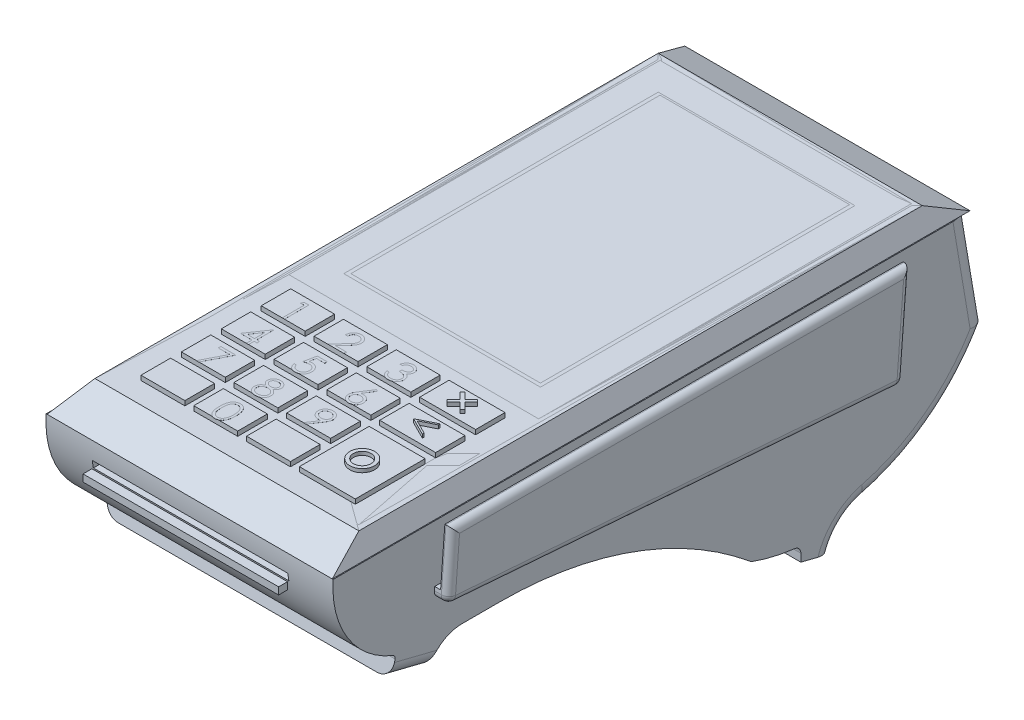
SolidWorks part; units mm, degrees
note: The reader was unsure of these and kept them because the rebuilt part matched: shared geometry of "Sketch5<2>", "Sketch7<2>", "Sketch8<2>", "Sketch9<2>".
material "ABS"
ref_plane "Front Plane" through (0, 0, 0) normal (0, 0, 1) x (1, 0, 0)
ref_plane "Top Plane" through (0, 0, 0) normal (0, 1, 0) x (1, 0, 0)
ref_plane "Right Plane" through (0, 0, 0) normal (1, 0, 0) x (0, 0, -1)
sketch "Sketch1" plane through (0, 0, 0) normal (0, 1, 0) x (1, 0, 0)
  line L1 (-35.75, -78) -> (35.75, -78)
  line L2 (-35.75, -78) -> (-35.75, 78)
  line L3 (-35.75, 78) -> (35.75, 78)
  line L4 (35.75, -78) -> (35.75, 78)
  line L5 (-35.75, -78) -> (35.75, 78) construction
  line L6 (-35.75, 78) -> (35.75, -78) construction
  point P0 (0, 0)
  dimension "D1" = 156
  dimension "D2" = 71.5
extrude "Boss-Extrude1" add sketch "Sketch1" against normal blind 5
sketch "Sketch2" plane through (0, 0, 0) normal (0, 1, 0) x (1, 0, 0)
  line L0 (-17.85, -35.4) -> (-15.35, -35.4) construction
  line L1 (-30.25, -39.55) -> (-17.85, -39.55)
  line L2 (-30.25, -39.55) -> (-30.25, -31.25)
  line L3 (-30.25, -31.25) -> (-17.85, -31.25)
  line L4 (-17.85, -39.55) -> (-17.85, -31.25)
  line L5 (-30.25, -39.55) -> (-17.85, -31.25) construction
  line L6 (-30.25, -31.25) -> (-17.85, -39.55) construction
  line L7 (-30.25, -50.825) -> (-17.85, -50.825)
  line L8 (-30.25, -50.825) -> (-30.25, -42.525)
  line L9 (-30.25, -42.525) -> (-17.85, -42.525)
  line L10 (-17.85, -50.825) -> (-17.85, -42.525)
  line L11 (-30.25, -50.825) -> (-17.85, -42.525) construction
  line L12 (-30.25, -42.525) -> (-17.85, -50.825) construction
  line L13 (-0.45, -39.55) -> (11.95, -39.55)
  line L14 (-0.45, -39.55) -> (-0.45, -31.25)
  line L15 (-0.45, -31.25) -> (11.95, -31.25)
  line L16 (11.95, -39.55) -> (11.95, -31.25)
  line L17 (-0.45, -39.55) -> (11.95, -31.25) construction
  line L18 (-0.45, -31.25) -> (11.95, -39.55) construction
  line L19 (-15.35, -39.55) -> (-2.95, -39.55)
  line L20 (-15.35, -39.55) -> (-15.35, -31.25)
  line L21 (-15.35, -31.25) -> (-2.95, -31.25)
  line L22 (-2.95, -39.55) -> (-2.95, -31.25)
  line L23 (-15.35, -39.55) -> (-2.95, -31.25) construction
  line L24 (-15.35, -31.25) -> (-2.95, -39.55) construction
  line L25 (-15.35, -50.825) -> (-2.95, -50.825)
  line L26 (-15.35, -50.825) -> (-15.35, -42.525)
  line L27 (-15.35, -42.525) -> (-2.95, -42.525)
  line L28 (-2.95, -50.825) -> (-2.95, -42.525)
  line L29 (-15.35, -50.825) -> (-2.95, -42.525) construction
  line L30 (-15.35, -42.525) -> (-2.95, -50.825) construction
  line L31 (-30.25, -62.1) -> (-17.85, -62.1)
  line L32 (-30.25, -62.1) -> (-30.25, -53.8)
  line L33 (-30.25, -53.8) -> (-17.85, -53.8)
  line L34 (-17.85, -62.1) -> (-17.85, -53.8)
  line L35 (-30.25, -62.1) -> (-17.85, -53.8) construction
  line L36 (-30.25, -53.8) -> (-17.85, -62.1) construction
  line L37 (-0.45, -50.825) -> (11.95, -50.825)
  line L38 (-0.45, -50.825) -> (-0.45, -42.525)
  line L39 (-0.45, -42.525) -> (11.95, -42.525)
  line L40 (11.95, -50.825) -> (11.95, -42.525)
  line L41 (-0.45, -50.825) -> (11.95, -42.525) construction
  line L42 (-0.45, -42.525) -> (11.95, -50.825) construction
  line L43 (-9.15, -62.1625) -> (-9.15, -65.1375) construction
  line L44 (-2.95, -35.4) -> (-0.45, -35.4) construction
  line L45 (-9.15, -53.8) -> (-9.15, -50.825) construction
  line L46 (-9.15, -42.525) -> (-9.15, -39.55) construction
  line L47 (-35.75, 78) -> (-35.75, -78) construction
  line L48 (11.95, -35.4) -> (14.45, -35.4) construction
  line L49 (-0.45, -73.5) -> (11.95, -73.5)
  line L50 (-0.45, -73.5) -> (-0.45, -65.1375)
  line L51 (-0.45, -65.1375) -> (11.95, -65.1375)
  line L52 (11.95, -73.5) -> (11.95, -65.1375)
  line L53 (-0.45, -73.5) -> (11.95, -65.1375) construction
  line L54 (-0.45, -65.1375) -> (11.95, -73.5) construction
  line L60 (14.45, -50.825) -> (30.25, -50.825)
  line L61 (-0.45, -62.1625) -> (11.95, -62.1625)
  line L62 (-0.45, -62.1625) -> (-0.45, -53.8)
  line L63 (-0.45, -53.8) -> (11.95, -53.8)
  line L64 (11.95, -62.1625) -> (11.95, -53.8)
  line L65 (-0.45, -62.1625) -> (11.95, -53.8) construction
  line L66 (-0.45, -53.8) -> (11.95, -62.1625) construction
  line L67 (-15.35, -62.1625) -> (-2.95, -62.1625)
  line L68 (-15.35, -62.1625) -> (-15.35, -53.8)
  line L69 (-15.35, -53.8) -> (-2.95, -53.8)
  line L70 (-2.95, -62.1625) -> (-2.95, -53.8)
  line L71 (-15.35, -62.1625) -> (-2.95, -53.8) construction
  line L72 (-15.35, -53.8) -> (-2.95, -62.1625) construction
  line L73 (-15.35, -73.5) -> (-2.95, -73.5)
  line L74 (-15.35, -73.5) -> (-15.35, -65.1375)
  line L75 (-15.35, -65.1375) -> (-2.95, -65.1375)
  line L76 (-2.95, -73.5) -> (-2.95, -65.1375)
  line L77 (-15.35, -73.5) -> (-2.95, -65.1375) construction
  line L78 (-15.35, -65.1375) -> (-2.95, -73.5) construction
  line L79 (-30.25, -73.5) -> (-17.85, -73.5)
  line L80 (-30.25, -73.5) -> (-30.25, -65.1375)
  line L81 (-30.25, -65.1375) -> (-17.85, -65.1375)
  line L82 (-17.85, -73.5) -> (-17.85, -65.1375)
  line L83 (-30.25, -73.5) -> (-17.85, -65.1375) construction
  line L84 (-30.25, -65.1375) -> (-17.85, -73.5) construction
  line L85 (-30.25, -57.95) -> (-35.75, -57.95) construction
  line L86 (30.25, -63.65) -> (35.75, -63.65) construction
  line L87 (35.75, -78) -> (35.75, 78) construction
  line L89 (14.45, -50.825) -> (14.45, -42.525)
  line L90 (14.45, -42.525) -> (30.25, -42.525)
  line L91 (30.25, -50.825) -> (30.25, -42.525)
  line L92 (14.45, -50.825) -> (30.25, -42.525) construction
  line L93 (14.45, -42.525) -> (30.25, -50.825) construction
  line L94 (14.45, -39.55) -> (30.25, -39.55)
  line L95 (14.45, -39.55) -> (14.45, -31.25)
  line L96 (14.45, -31.25) -> (30.25, -31.25)
  line L97 (30.25, -39.55) -> (30.25, -31.25)
  line L98 (14.45, -39.55) -> (30.25, -31.25) construction
  line L99 (14.45, -31.25) -> (30.25, -39.55) construction
  line L100 (14.45, -73.5) -> (30.25, -73.5)
  line L101 (14.45, -73.5) -> (14.45, -53.8)
  line L102 (14.45, -53.8) -> (30.25, -53.8)
  line L103 (30.25, -73.5) -> (30.25, -53.8)
  line L104 (14.45, -73.5) -> (30.25, -53.8) construction
  line L105 (14.45, -53.8) -> (30.25, -73.5) construction
  line L108 (22.35, -73.5) -> (22.35, -78) construction
  line L109 (-35.75, -78) -> (35.75, -78) construction
  point P0 (-24.05, -35.4)
  point P5 (-24.05, -46.675)
  point P10 (5.75, -35.4)
  point P15 (-9.15, -35.4)
  point P20 (-9.15, -46.675)
  point P25 (-24.05, -57.95)
  point P30 (5.75, -46.675)
  point P45 (22.35, -46.675)
  point P47 (5.75, -69.3188)
  point P57 (5.75, -57.9813)
  point P62 (-9.15, -57.9813)
  point P67 (-9.15, -69.3188)
  point P72 (-24.05, -69.3187)
  point P87 (22.35, -35.4)
  point P92 (22.35, -63.65)
  dimension "D1" = 8.3
  dimension "D2" = 12.4
  dimension "D4" = 15.8
  dimension "D5" = 19.7
  dimension "D6" = 42.25
  dimension "D7" = 4.5
  dimension "D3" = 5.5
extrude "Boss-Extrude2" add sketch "Sketch2" along normal blind 1.3
sketch "Sketch3" plane through (0, 1.3, 0) normal (0, 1, 0) x (1, 0, 0)
  line L0 (14.45, -53.8) -> (30.25, -73.5) construction
  line L1 (30.25, -53.8) -> (14.45, -73.5) construction
  line L2 (14.45, -42.525) -> (30.25, -50.825) construction
  line L3 (30.25, -42.525) -> (14.45, -50.825) construction
  line L4 (14.45, -39.55) -> (30.25, -31.25) construction
  line L5 (14.45, -31.25) -> (30.25, -39.55) construction
  line L12 (19.85, -46.675) -> (24.85, -46.675) construction
  line L13 (19.85, -46.675) -> (24.85, -44.175)
  line L14 (19.85, -46.675) -> (24.85, -49.175)
  line L15 (20.85, -46.675) -> (24.85, -44.675)
  line L16 (24.85, -44.675) -> (24.85, -44.175)
  line L17 (20.85, -46.675) -> (24.85, -48.675)
  line L18 (24.85, -48.675) -> (24.85, -49.175)
  line L19 (20.2036, -33.2536) -> (24.4964, -37.5464) construction
  line L20 (20.2036, -37.5464) -> (24.4964, -33.2536) construction
  line L21 (20.5571, -37.9) -> (22.35, -36.1071)
  line L22 (19.85, -33.6071) -> (21.6429, -35.4)
  line L23 (19.85, -37.1929) -> (21.6429, -35.4)
  line L24 (20.5571, -32.9) -> (22.35, -34.6929)
  line L25 (19.85, -33.6071) -> (20.5571, -32.9)
  line L26 (24.1429, -32.9) -> (24.85, -33.6071)
  line L27 (24.85, -37.1929) -> (24.1429, -37.9)
  line L28 (19.85, -37.1929) -> (20.5571, -37.9)
  line L29 (22.35, -36.1071) -> (24.1429, -37.9)
  line L30 (19.85, -33.6071) -> (24.1429, -37.9) construction
  line L31 (22.35, -34.6929) -> (24.1429, -32.9)
  line L32 (19.85, -37.1929) -> (24.1429, -32.9) construction
  line L33 (23.0571, -35.4) -> (24.85, -37.1929)
  line L34 (20.5571, -32.9) -> (24.85, -37.1929) construction
  line L35 (23.0571, -35.4) -> (24.85, -33.6071)
  line L36 (20.5571, -37.9) -> (24.85, -33.6071) construction
  line L37 (22.35, -34.6929) -> (22.35, -31.25) construction
  line L38 (30.25, -31.25) -> (14.45, -31.25) construction
  circle A0 centre (22.35, -63.65) radius 2.5
  circle A1 centre (22.35, -63.65) radius 3.5
  point P35 (22.35, -46.675)
  point P39 (22.35, -35.4)
  dimension "D1" = 5
  dimension "D2" = 7
  dimension "D3" = 5
  dimension "D4" = 5
  dimension "D5" = 1
  dimension "D6" = 0.5
  dimension "D8" = 5
  dimension "D9" = 5
  dimension "D7" = 0.5
extrude "Boss-Extrude3" add sketch "Sketch3" along normal blind 1
sketch "Sketch4" plane through (0, 1.3, 0) normal (0, 1, 0) x (1, 0, 0)
  line L0 (-30.25, -39.55) -> (-17.85, -39.55) construction
  line L1 (-30.25, -62.1) -> (-17.85, -62.1) construction
  line L2 (-15.35, -62.1625) -> (-2.95, -62.1625) construction
  line L3 (-15.35, -39.55) -> (-2.95, -39.55) construction
  line L4 (-0.45, -50.825) -> (11.95, -50.825) construction
  line L5 (-15.35, -73.5) -> (-2.95, -73.5) construction
  line L9 (-0.45, -39.55) -> (11.95, -39.55) construction
  line L15 (-30.25, -50.825) -> (-17.85, -50.825) construction
  line L18 (-15.35, -50.825) -> (-2.95, -50.825) construction
  line L21 (-0.45, -62.1625) -> (11.95, -62.1625) construction
  text T0 "1" font "Century Gothic" height in points 26
  text T1 "2" font "Century Gothic" height in points 26
  text T2 "3" font "Century Gothic" height in points 26
  text T3 "4" font "Century Gothic" height in points 26
  text T4 "5" font "Century Gothic" height in points 26
  text T5 "7" font "Century Gothic" height in points 26
  text T6 "8" font "Century Gothic" height in points 26
  text T7 "9" font "Century Gothic" height in points 26
  text T8 "0" font "Century Gothic" height in points 26
  text T9 "6" font "Century Gothic" height in points 26
sketch "Sketch5" plane through (0, 0, 0) normal (0, 1, 0) x (1, 0, 0)
  line L0 (-37.25, -79.5) -> (-37.25, 79.5)
  line L1 (-35.75, -78) -> (35.75, -78)
  line L2 (-35.75, -78) -> (-35.75, 78)
  line L3 (-35.75, 78) -> (35.75, 78)
  line L4 (35.75, -78) -> (35.75, 78)
  line L5 (-35.75, -78) -> (35.75, 78) construction
  line L6 (-35.75, 78) -> (35.75, -78) construction
  line L7 (-37.25, 79.5) -> (37.25, 79.5)
  line L8 (37.25, -79.5) -> (37.25, 79.5)
  line L9 (-37.25, -79.5) -> (37.25, -79.5)
  point P0 (0, 0)
  dimension "D1" = 156
  dimension "D2" = 71.5
  dimension "D3" = 1.5
extrude "Boss-Extrude4" add sketch "Sketch5" against normal up to surface (5 mm away) separate body up to face at (0, -5, 0)
sketch "Sketch6" plane through (0, -5, 0) normal (0, -1, 0) x (1, 0, 0)
  line L1 (-40.25, -90) -> (40.25, -90)
  line L2 (-40.25, -90) -> (-40.25, 90)
  line L3 (-40.25, 90) -> (40.25, 90)
  line L4 (40.25, -90) -> (40.25, 90)
  line L5 (-40.25, -90) -> (40.25, 90) construction
  line L6 (-40.25, 90) -> (40.25, -90) construction
  point P0 (0, 0)
  dimension "D1" = 180
  dimension "D2" = 80.5
loft "Loft1" add profiles "Sketch6" section "Sketch6" section "Sketch5<2>"
sketch "Sketch5<2>" plane through (0, 0, 0) normal (0, 1, 0) x (1, 0, 0) same geometry as "Sketch5"
sketch "Sketch7" plane through (0, 0, 0) normal (0, 1, 0) x (1, 0, 0)
  line L0 (37.25, -79.5) -> (37.25, 79.5) construction
  line L1 (-35.25, 78.5) -> (35.25, 78.5)
  line L2 (-35.25, 78.5) -> (-35.25, -26.75)
  line L3 (-35.25, -26.75) -> (35.25, -26.75)
  line L4 (35.25, 78.5) -> (35.25, -26.75)
  line L7 (-2.95, -31.25) -> (-15.35, -31.25) construction
  line L8 (-37.25, 79.5) -> (37.25, 79.5) construction
  line L9 (-37.25, 79.5) -> (-37.25, -79.5) construction
  dimension "D1" = 2
  dimension "D2" = 1
  dimension "D3" = 2
  dimension "D4" = 4.5
extrude "Cut-Extrude2" cut sketch "Sketch7" against normal blind 3
extrude "Boss-Extrude5" add sketch "Sketch7<2>" against normal blind 3 separate body
sketch "Sketch7<2>" plane through (0, 0, 0) normal (0, 1, 0) x (1, 0, 0) same geometry as "Sketch7"
sketch "Sketch8" plane through (0, 0, 0) normal (0, 1, 0) x (1, 0, 0)
  line L0 (35.75, -78) -> (35.75, 78) construction
  line L1 (27.75, 70) -> (-27.75, 70)
  line L2 (27.75, 70) -> (27.75, -18.75)
  line L3 (27.75, -18.75) -> (-27.75, -18.75)
  line L4 (-27.75, 70) -> (-27.75, -18.75)
  line L5 (-35.25, -26.75) -> (35.25, -26.75) construction
  line L6 (-35.75, 78) -> (-35.75, -78) construction
  line L7 (35.75, 78) -> (-35.75, 78) construction
  dimension "D1" = 8
  dimension "D2" = 8
  dimension "D3" = 8
  dimension "D4" = 8
extrude "Cut-Extrude3" cut sketch "Sketch8" against normal blind 3
extrude "Boss-Extrude6" add sketch "Sketch8<2>" against normal blind 3 separate body
sketch "Sketch8<2>" plane through (0, 0, 0) normal (0, 1, 0) x (1, 0, 0) same geometry as "Sketch8"
sketch "Sketch9" plane through (0, 0, 0) normal (0, 1, 0) x (1, 0, 0)
  line L0 (27.75, -18.75) -> (27.75, 70) construction
  line L1 (-26.75, 69.5) -> (26.75, 69.5)
  line L2 (-26.75, 69.5) -> (-26.75, -17.75)
  line L3 (-26.75, -17.75) -> (26.75, -17.75)
  line L4 (26.75, 69.5) -> (26.75, -17.75)
  line L5 (27.75, 70) -> (-27.75, 70) construction
  line L6 (-27.75, 70) -> (-27.75, -18.75) construction
  line L7 (-27.75, -18.75) -> (27.75, -18.75) construction
  dimension "D1" = 1
  dimension "D2" = 0.5
  dimension "D3" = 1
  dimension "D4" = 1
extrude "Cut-Extrude4" cut sketch "Sketch9" against normal blind 3
extrude "Boss-Extrude7" add sketch "Sketch9<2>" against normal blind 3 separate body
sketch "Sketch9<2>" plane through (0, 0, 0) normal (0, 1, 0) x (1, 0, 0) same geometry as "Sketch9"
sketch "Sketch10" plane through (0, 0, 0) normal (1, 0, 0) x (0, 0, -1)
  line L0 (-90, -5) -> (90, -5)
  line L2 (-63, -34) -> (-63, -5) construction
  line L3 (-63, -34) -> (-43, -34)
  line L5 (-90, -5) -> (-90, -34.5804) construction
  line L6 (90, -5) -> (95, -34.5804)
  line L7 (90, -5) -> (79.5, 0) construction
  line L8 (46.8494, -63) -> (46.8494, -5) construction
  line L9 (-90, -34.5804) -> (95, -34.5804) construction
  arc A4 (95, -34.5804) -> (28, -59.6691) centre (46.8494, -8) cw
  arc A5 (-90, -5) -> (-63, -34) centre (-63, -6.931) ccw
  arc A6 (-43, -34) -> (28, -59.6691) centre (-43, -145.0264) cw
  dimension "D2" = 29
  dimension "D3" = 27
  dimension "D4" = 185
  dimension "D5" = 20
  dimension "D9" = 30
  dimension "D11" = 58
  dimension "D12" = 55
  dimension "D13" = 67
extrude "Boss-Extrude8" add sketch "Sketch10" along normal mid plane 81 separate body
extrude "Boss-Extrude9" add sketch "Sketch4" along normal blind 0.01
ref_plane "Plane1" through (0, 0, 90) normal (0, 0, 1) x (1, 0, 0)
sketch "Sketch12" plane through (0, 0, 90) normal (0, 0, 1) x (1, 0, 0)
  line L0 (0, 0) -> (0, -12) construction
  line L2 (-27.6, -12) -> (27.6, -12)
  line L3 (27.6, -12) -> (27.6, -14)
  line L4 (27.6, -14) -> (-27.6, -14)
  line L5 (-27.6, -14) -> (-27.6, -12)
  point P7 (0, -12)
  dimension "D1" = 12
  dimension "D2" = 55.2
  dimension "D3" = 2
extrude "Boss-Extrude10" add sketch "Sketch12" along normal blind 2.5
sketch "Sketch13" plane through (0, 0, 90) normal (0, 0, 1) x (1, 0, 0)
  line L0 (27.6, -12) -> (27.6, -10)
  line L1 (-27.6, -12) -> (-27.6, -10)
  line L2 (-27.6, -10) -> (27.6, -10)
  line L3 (27.6, -12) -> (-27.6, -12)
  dimension "D1" = 2
extrude "Cut-Extrude5" cut sketch "Sketch13" against normal mid plane 20
sketch "Sketch14" plane through (40.5, 0, 0) normal (1, 0, 0) x (0, 0, -1)
  line L0 (46.8494, -63) -> (46.8494, -68) construction
  line L1 (41.9991, -66.7857) -> (51.6997, -69.2143)
  line L2 (51.6997, -69.2143) -> (51.6997, -62.7857)
  line L3 (41.9991, -66.7857) -> (41.9991, -62.7857)
  arc A0 (28, -59.6691) -> (95, -34.5804) centre (46.8494, -8) ccw construction
  arc A1 (41.9991, -62.7857) -> (51.6997, -62.7857) centre (46.8494, -8) ccw
  point P11 (46.8494, -68)
  dimension "D2" = 10
  dimension "D1" = 5
  dimension "D3" = 4
extrude "Boss-Extrude11" add sketch "Sketch14" against normal blind 8
mirror "Mirror1" about plane through (0, 0, 0) normal (1, 0, 0) of "Boss-Extrude11"
fillet "Fillet1" radius 12.5 2 edges at (-36.5, -62.7857, -51.6997) (36.5, -62.7857, -51.6997)
fillet "Fillet2" radius 2 2 edges at (-36.5, -62.7857, -41.9991) (36.5, -62.7857, -41.9991)
sketch "Sketch17" plane through (40.5, 0, 0) normal (1, 0, 0) x (0, 0, -1)
  line L0 (51.6997, -69.2143) -> (41.9991, -66.7857) construction
  line L1 (41.9991, -66.7857) -> (-63, -40.499) construction
  line L2 (-63, -34) -> (-63, -40.499)
  line L3 (-63, -34) -> (-43, -34) construction
  line L4 (-63, -40.499) -> (-73.6707, -37.8275)
  line L5 (-73.6707, -37.8275) -> (-72.2999, -32.3523)
  arc A0 (-90, -5) -> (-63, -34) centre (-63, -6.931) ccw construction
  arc A1 (-72.2999, -32.3523) -> (-63, -34) centre (-63, -6.931) ccw
  dimension "D1" = 11
extrude "Boss-Extrude12" add sketch "Sketch17" against normal up to surface (81 mm away) up to face at (-40.5, -45.3563, -22.8493)
fillet "Fillet3" radius 1 1 edges at (0, -32.3523, 72.2999)
fillet "Fillet4" radius 10 1 edges at (0, -34, 63)
fillet "Fillet5" radius 4 2 edges at (-40.5, -39.1633, 68.3353) (40.5, -39.1633, 68.3353)
sketch "Sketch18" plane through (0, 15.1248, 60.414) normal (0, 0.2429, 0.9701) x (1, 0, 0)
  line L0 (0, -54.5865) -> (0, -51.5865) construction
  line L1 (-36.5, -54.5865) -> (36.5, -54.5865) construction
  line L2 (-29, -51.5865) -> (29, -51.5865)
  line L3 (-29, -51.5865) -> (-29, -49.8275)
  line L4 (40.5, -49.8275) -> (-40.5, -49.8275) construction
  line L5 (-29, -49.8275) -> (29, -49.8275)
  line L6 (29, -49.8275) -> (29, -51.5865)
  point P7 (0, -51.5865)
  dimension "D1" = 3
  dimension "D2" = 58
extrude "Cut-Extrude6" cut sketch "Sketch18" against normal up to next
fillet "Fillet11" radius 5 6 edges at (-40.5, -64.1752, -55.0588) (40.5, -64.1752, -55.0588) (-40.5, -51.5305, -80.4663) (40.5, -51.5305, -80.4663) (-40.5, -19.7902, -92.5) (40.5, -19.7902, -92.5)
sketch "Sketch19" plane through (40.5, 0, 0) normal (1, 0, 0) x (0, 0, -1)
  line L0 (67, -5) -> (67, -34) construction
  line L1 (84.9291, -5) -> (-90, -5) construction
  line L2 (-61.6118, -5) -> (-61.6118, -24) construction
  line L4 (67, -34) -> (95, -34.5804) construction
  line L5 (67, -34) -> (67.5426, -27.0211)
  line L6 (-61.6118, -24) -> (67, -34)
  line L7 (-61.6118, -24) -> (-61.3793, -21.009)
  line L8 (-61.3793, -21.009) -> (67.5426, -27.0211)
  dimension "D1" = 29
  dimension "D2" = 19
  dimension "D3" = 28
  dimension "D4" = 129
  dimension "D5" = 7
  dimension "D6" = 3
extrude "Boss-Extrude13" add sketch "Sketch19" along normal blind 1.7
sketch "Sketch20" plane through (42.2, 0, 0) normal (1, 0, 0) x (0, 0, -1)
  line L0 (67, -34) -> (67.5426, -27.0211)
  line L1 (67.5426, -27.0211) -> (69.1705, -6.0843)
  line L2 (-61.6118, -24) -> (-61.3793, -21.009)
  line L3 (-61.3793, -21.009) -> (-60.1777, -5.5557)
  line L4 (69.1705, -6.0843) -> (-60.1777, -5.5557)
  line L5 (67, -34) -> (-61.6118, -24)
  dimension "D1" = 28
  dimension "D2" = 18.5
extrude "Boss-Extrude14" add sketch "Sketch20" along normal blind 2.3
fillet "Fillet12" radius 2 3 edges at (44.5, -20.0421, -68.0853) (44.5, -14.7778, 60.8948) (44.5, -5.82, -4.4964)
fillet "Fillet13" radius 2 5 edges at (44.5, -29, -2.6941) (41.5, -34, -67) (41.5, -24, 61.6118) (43.9142, -24.0454, 61.0278) (43.9142, -33.9546, -66.416)
ref_plane "Plane2" through (0, -59.6691, 0) normal (0, 1, 0) x (1, 0, 0)
sketch "Sketch21" plane through (0, -59.6691, 0) normal (0, 1, 0) x (1, 0, 0)
  line L0 (0, -63) -> (0, -13) construction
  line L1 (-36.5, -63) -> (36.5, -63) construction
  line L2 (-29.4, -13) -> (29.4, -13)
  line L3 (29.4, -13) -> (29.4, 4)
  line L4 (29.4, 4) -> (-29.4, 4) construction
  line L5 (-29.4, 4) -> (-29.4, -13)
  line L6 (-30.25, 4) -> (30.25, 4) construction
  line L7 (30.25, 4) -> (30.25, 29)
  line L8 (30.25, 29) -> (-30.25, 29)
  line L9 (-30.25, 29) -> (-30.25, 4)
  line L10 (-29.4, 4) -> (-30.25, 4)
  line L11 (29.4, 4) -> (30.25, 4)
  point P8 (0, -13)
  point P13 (0, 4)
  dimension "D1" = 50
  dimension "D2" = 58.8
  dimension "D3" = 17
  dimension "D4" = 60.5
  dimension "D5" = 25
extrude "Cut-Extrude7" cut sketch "Sketch21" along normal blind 33 and the other way through all
sketch "Sketch23" plane through (0, -26.6691, 0) normal (0, -1, 0) x (1, 0, 0)
  line L0 (29.4, 13) -> (-29.4, 13)
  line L1 (-29.4, 13) -> (-29.4, -4)
  line L2 (-29.4, -4) -> (29.4, -4)
  line L3 (29.4, -4) -> (29.4, 13)
extrude "Boss-Extrude15" add sketch "Sketch23" along normal blind 7
sketch "Sketch25" plane through (0, -26.6691, 0) normal (0, -1, 0) x (1, 0, 0)
  line L0 (30.25, -29) -> (-30.25, -29)
  line L1 (-30.25, -29) -> (-30.25, -24)
  line L2 (-30.25, -29) -> (-30.25, -4) construction
  line L3 (-30.25, -24) -> (30.25, -24)
  line L4 (30.25, -4) -> (30.25, -28) construction
  line L5 (30.25, -24) -> (30.25, -29)
  dimension "D1" = 5
extrude "Boss-Extrude16" add sketch "Sketch25" along normal blind 5
sketch "Sketch26" plane through (0, -26.6691, 0) normal (0, -1, 0) x (1, 0, 0)
  line L0 (-30.25, -24) -> (-25.25, -24)
  line L1 (30.25, -24) -> (-30.25, -24) construction
  line L2 (-25.25, -24) -> (-25.25, -20)
  line L3 (-25.25, -20) -> (-30.25, -20)
  line L4 (-30.25, -28) -> (-30.25, -4) construction
  line L5 (-30.25, -20) -> (-30.25, -24)
  dimension "D1" = 4
  dimension "D2" = 5
extrude "Boss-Extrude17" add sketch "Sketch26" along normal blind 3
sketch "Sketch27" plane through (0, -33.6691, 0) normal (0, -1, 0) x (1, 0, 0)
  line L0 (-29.24, -2.65) -> (-15.24, -2.65)
  line L1 (-15.08, -2.65) -> (0.92, -2.65)
  line L2 (-15.08, -2.65) -> (-15.08, 11.65)
  line L3 (-15.08, 11.65) -> (0.92, 11.65)
  line L4 (0.92, -2.65) -> (0.92, 11.65)
  line L5 (-15.08, -2.65) -> (0.92, 11.65) construction
  line L6 (-15.08, 11.65) -> (0.92, -2.65) construction
  line L7 (-29.24, -2.65) -> (-29.24, 11.65)
  line L8 (-29.24, 11.65) -> (-15.24, 11.65)
  line L9 (-15.24, -2.65) -> (-15.24, 11.65)
  line L10 (-29.24, -2.65) -> (-15.24, 11.65) construction
  line L11 (-29.24, 11.65) -> (-15.24, -2.65) construction
  line L12 (15.24, -2.65) -> (29.24, -2.65)
  line L13 (15.24, -2.65) -> (15.24, 11.65)
  line L14 (15.24, 11.65) -> (29.24, 11.65)
  line L15 (29.24, -2.65) -> (29.24, 11.65)
  line L16 (15.24, -2.65) -> (29.24, 11.65) construction
  line L17 (15.24, 11.65) -> (29.24, -2.65) construction
  line L18 (1.08, -2.65) -> (15.08, -2.65)
  line L19 (1.08, -2.65) -> (1.08, 11.65)
  line L20 (1.08, 11.65) -> (15.08, 11.65)
  line L21 (15.08, -2.65) -> (15.08, 11.65)
  line L22 (1.08, -2.65) -> (15.08, 11.65) construction
  line L23 (1.08, 11.65) -> (15.08, -2.65) construction
  line L24 (-29.4, 4.5) -> (29.4, 4.5) construction
  line L25 (-29.4, -4) -> (-29.4, 13) construction
  line L26 (29.4, 13) -> (29.4, -4) construction
  line L27 (29.4, 11.65) -> (29.24, 11.65) construction
  line L28 (15.24, 11.65) -> (15.08, 11.65) construction
  line L29 (1.08, 11.65) -> (0.92, 11.65) construction
  line L30 (-15.08, 11.65) -> (-15.24, 11.65) construction
  line L31 (-29.24, 11.65) -> (-29.4, 11.65) construction
  point P0 (-7.08, 4.5)
  point P5 (-22.24, 4.5)
  point P10 (22.24, 4.5)
  point P15 (8.08, 4.5)
  dimension "D1" = 16
  dimension "D2" = 14.3
  dimension "D3" = 14
  dimension "D4" = 14.3
  dimension "D5" = 14
  dimension "D6" = 14.3
  dimension "D7" = 14
  dimension "D8" = 14.3
extrude "Boss-Extrude18" add sketch "Sketch27" against normal blind 20 and the other way blind 0.1 separate body
sketch "Sketch28" plane through (0, -33.7691, 0) normal (0, -1, 0) x (1, 0, 0)
  line L8 (16.74, -0.5) -> (27.74, -0.5)
  line L18 (-27.74, -0.5) -> (-16.74, -0.5)
  line L19 (2.58, -0.5) -> (13.58, -0.5)
  line L20 (13.58, -0.5) -> (13.58, 4.5)
  line L21 (2.58, -0.5) -> (2.58, 4.5)
  line L22 (2.58, 4.5) -> (5.58, 4.5) construction
  line L23 (13.58, 4.5) -> (10.58, 4.5) construction
  line L24 (5.58, 4.5) -> (5.58, 9.5) construction
  line L25 (5.58, 9.5) -> (10.58, 9.5)
  line L26 (10.58, 9.5) -> (10.58, 4.5) construction
  line L27 (8.08, 9.5) -> (8.08, -0.5) construction
  line L28 (-16.74, -0.5) -> (-16.74, 4.5)
  line L31 (8.08, 11.65) -> (8.08, -2.65) construction
  line L32 (10.58, 9.5) -> (10.58, 8)
  line L33 (12.58, 4.5) -> (13.58, 4.5)
  line L34 (-7.08, 11.65) -> (-7.08, -2.65) construction
  line L35 (3.58, 4.5) -> (2.58, 4.5)
  line L36 (3.58, 6) -> (3.58, 4.5)
  line L37 (27.74, -0.5) -> (27.74, 4.5)
  line L40 (-13.83, -0.5) -> (-0.33, -0.5)
  line L41 (-0.33, -0.5) -> (-0.33, 4.5)
  line L42 (-13.83, -0.5) -> (-13.83, 4.5)
  line L43 (-13.83, 4.5) -> (-8.83, 4.5) construction
  line L44 (-0.33, 4.5) -> (-5.33, 4.5) construction
  line L45 (-8.83, 4.5) -> (-8.83, 9.5) construction
  line L46 (-8.83, 9.5) -> (-5.33, 9.5)
  line L47 (-5.33, 9.5) -> (-5.33, 4.5) construction
  line L48 (-7.08, 9.5) -> (-7.08, -0.5) construction
  line L49 (0.92, 11.65) -> (-15.08, 11.65) construction
  line L50 (-15.08, -2.65) -> (0.92, -2.65) construction
  line L51 (15.08, 11.65) -> (1.08, 11.65) construction
  line L52 (1.08, -2.65) -> (15.08, -2.65) construction
  line L53 (10.58, 7) -> (11.58, 7) construction
  line L54 (11.58, 8) -> (10.58, 8)
  line L55 (11.58, 8) -> (11.58, 6)
  line L56 (11.58, 6) -> (12.58, 6)
  line L57 (12.58, 6) -> (12.58, 4.5)
  line L58 (4.58, 6) -> (3.58, 6)
  line L59 (4.58, 8) -> (4.58, 6)
  line L60 (4.58, 8) -> (5.58, 8)
  line L61 (5.58, 9.5) -> (5.58, 8)
  line L62 (16.74, -0.5) -> (16.74, 4.5)
  line L63 (16.74, 4.5) -> (19.74, 4.5) construction
  line L65 (27.74, 4.5) -> (24.74, 4.5) construction
  line L66 (19.74, 4.5) -> (19.74, 9.5) construction
  line L67 (19.74, 9.5) -> (24.74, 9.5)
  line L68 (24.74, 9.5) -> (24.74, 4.5) construction
  line L69 (22.24, 9.5) -> (22.24, -0.5) construction
  line L70 (22.24, 11.65) -> (22.24, -2.65) construction
  line L71 (24.74, 9.5) -> (24.74, 8)
  line L72 (26.74, 4.5) -> (27.74, 4.5)
  line L73 (17.74, 4.5) -> (16.74, 4.5)
  line L74 (17.74, 6) -> (17.74, 4.5)
  line L75 (24.74, 7) -> (25.74, 7) construction
  line L76 (25.74, 8) -> (24.74, 8)
  line L77 (25.74, 8) -> (25.74, 6)
  line L78 (25.74, 6) -> (26.74, 6)
  line L79 (26.74, 6) -> (26.74, 4.5)
  line L80 (18.74, 6) -> (17.74, 6)
  line L81 (18.74, 8) -> (18.74, 6)
  line L82 (18.74, 8) -> (19.74, 8)
  line L83 (19.74, 9.5) -> (19.74, 8)
  line L84 (29.24, 11.65) -> (15.24, 11.65) construction
  line L85 (15.24, -2.65) -> (29.24, -2.65) construction
  line L86 (-27.74, -0.5) -> (-27.74, 4.5)
  line L87 (-27.74, 4.5) -> (-24.74, 4.5) construction
  line L88 (-16.74, 4.5) -> (-19.74, 4.5) construction
  line L89 (-24.74, 4.5) -> (-24.74, 9.5) construction
  line L90 (-24.74, 9.5) -> (-19.74, 9.5)
  line L91 (-19.74, 9.5) -> (-19.74, 4.5) construction
  line L92 (-22.24, 9.5) -> (-22.24, -0.5) construction
  line L93 (-22.24, 11.65) -> (-22.24, -2.65) construction
  line L94 (-19.74, 9.5) -> (-19.74, 8)
  line L95 (-17.74, 4.5) -> (-16.74, 4.5)
  line L96 (-26.74, 4.5) -> (-27.74, 4.5)
  line L97 (-26.74, 6) -> (-26.74, 4.5)
  line L98 (-19.74, 7) -> (-18.74, 7) construction
  line L99 (-18.74, 8) -> (-19.74, 8)
  line L100 (-18.74, 8) -> (-18.74, 6)
  line L101 (-18.74, 6) -> (-17.74, 6)
  line L102 (-17.74, 6) -> (-17.74, 4.5)
  line L103 (-25.74, 6) -> (-26.74, 6)
  line L104 (-25.74, 8) -> (-25.74, 6)
  line L105 (-25.74, 8) -> (-24.74, 8)
  line L106 (-24.74, 9.5) -> (-24.74, 8)
  line L107 (-15.24, 11.65) -> (-29.24, 11.65) construction
  line L108 (-29.24, -2.65) -> (-15.24, -2.65) construction
  line L109 (-5.33, 7) -> (-3.33, 7) construction
  line L110 (-3.33, 8) -> (-3.33, 6)
  line L111 (-3.33, 8) -> (-5.33, 8)
  line L112 (-5.33, 8) -> (-5.33, 9.5)
  line L113 (-3.33, 6) -> (-1.83, 6)
  line L114 (-1.83, 6) -> (-1.83, 4.5)
  line L115 (-1.83, 4.5) -> (-0.33, 4.5)
  line L116 (-8.83, 7) -> (-10.83, 7) construction
  line L117 (-12.33, 4.5) -> (-13.83, 4.5)
  line L118 (-12.33, 6) -> (-12.33, 4.5)
  line L119 (-10.83, 6) -> (-12.33, 6)
  line L120 (-10.83, 8) -> (-10.83, 6)
  line L121 (-10.83, 8) -> (-8.83, 8)
  line L122 (-8.83, 8) -> (-8.83, 9.5)
  point P7 (25.74, 7)
  point P19 (11.58, 7)
  point P27 (-18.74, 7)
  point P59 (8.08, 4.5)
  point P71 (-7.08, 4.5)
  point P85 (22.24, 4.5)
  point P100 (-22.24, 4.5)
  point P113 (-3.33, 7)
  dimension "D2" = 10
  dimension "D3" = 5
  dimension "D4" = 11
  dimension "D5" = 10
  dimension "D6" = 5
  dimension "D7" = 11
  dimension "D8" = 3
  dimension "D9" = 10
  dimension "D10" = 5
  dimension "D11" = 11
  dimension "D12" = 3
  dimension "D13" = 10
  dimension "D14" = 5
  dimension "D15" = 13.5
  dimension "D16" = 5
  dimension "D17" = 1
  dimension "D18" = 2
  dimension "D19" = 3
  dimension "D20" = 1
  dimension "D21" = 2
  dimension "D22" = 1
  dimension "D23" = 2
  dimension "D24" = 2
  dimension "D25" = 2
  dimension "D26" = 1.5
extrude "Cut-Extrude9" cut sketch "Sketch28" against normal blind 15
sketch "Sketch29" plane through (0, -26.6691, 0) normal (0, -1, 0) x (1, 0, 0)
  line L0 (-27.25, -4) -> (-27.25, -5) construction
  line L1 (-30.25, -4) -> (30.25, -4) construction
  line L2 (-27.25, -5) -> (-30.25, -5) construction
  line L3 (-30.25, -20) -> (-30.25, -4) construction
  line L4 (-27.25, -5) -> (-18.25, -5)
  line L5 (-18.25, -5) -> (-18.25, -16.7)
  line L6 (-18.25, -16.7) -> (-27.25, -16.7)
  line L7 (-27.25, -16.7) -> (-27.25, -5)
  dimension "D1" = 1
  dimension "D2" = 3
  dimension "D3" = 9
  dimension "D4" = 11.7
extrude "Boss-Extrude19" add sketch "Sketch29" against normal blind 20 and the other way blind 0.1 separate body
sketch "Sketch30" plane through (0, -26.7691, 0) normal (0, -1, 0) x (1, 0, 0)
  line L0 (-27.25, -5) -> (-18.25, -16.7) construction
  line L1 (-22.75, -10.85) -> (-22.75, -9.85) construction
  circle A0 centre (-22.75, -9.85) radius 3.15
  dimension "D1" = 6.3
  dimension "D2" = 1
extrude "Cut-Extrude10" cut sketch "Sketch30" against normal blind 15
sketch "Sketch31" plane through (0, -11.7691, 0) normal (0, -1, 0) x (1, 0, 0)
  circle A0 centre (-22.75, -9.85) radius 1
  dimension "D1" = 2
extrude "Boss-Extrude20" add sketch "Sketch31" along normal blind 10
fillet "Fillet14" radius 1 1 edges at (-22.75, -21.7691, -10.85)
sketch "Sketch33" plane through (0, -26.6691, 0) normal (0, -1, 0) x (1, 0, 0)
  line L0 (-29.4, -4) -> (29.4, -4) construction
  line L1 (12.75, -6) -> (27.25, -6)
  line L2 (12.75, -6) -> (12.75, -22.5)
  line L3 (12.75, -22.5) -> (27.25, -22.5)
  line L4 (27.25, -6) -> (27.25, -22.5)
  line L5 (12.75, -6) -> (27.25, -22.5) construction
  line L6 (12.75, -22.5) -> (27.25, -6) construction
  line L7 (30.25, -4) -> (30.25, -24) construction
  point P0 (20, -14.25)
  dimension "D1" = 16.5
  dimension "D2" = 14.5
  dimension "D3" = 2
  dimension "D4" = 3
extrude "Boss-Extrude21" add sketch "Sketch33" against normal blind 20 and the other way blind 0.1 separate body
sketch "Sketch34" plane through (0, -26.7691, 0) normal (0, -1, 0) x (1, 0, 0)
  line L3 (23.5, -16.75) -> (25, -16.75)
  line L4 (23.5, -17.75) -> (23.5, -16.75)
  line L5 (21.5, -17.75) -> (23.5, -17.75)
  line L7 (20, -18.75) -> (21.5, -18.75)
  line L8 (20, -19.75) -> (20, -18.75)
  line L9 (21.5, -18.75) -> (21.5, -17.75)
  line L14 (15, -19.75) -> (20, -19.75)
  line L23 (12.75, -14.25) -> (27.25, -14.25) construction
  line L24 (12.75, -6) -> (12.75, -22.5) construction
  line L25 (27.25, -22.5) -> (27.25, -6) construction
  line L26 (15, -8.75) -> (15, -19.75)
  line L27 (15, -8.75) -> (20, -8.75)
  line L28 (21.5, -9.75) -> (21.5, -10.75)
  line L29 (20, -8.75) -> (20, -9.75)
  line L30 (20, -9.75) -> (21.5, -9.75)
  line L31 (21.5, -10.75) -> (23.5, -10.75)
  line L32 (23.5, -10.75) -> (23.5, -11.75)
  line L33 (23.5, -11.75) -> (25, -11.75)
  line L34 (25, -11.75) -> (25, -16.75)
  line L35 (15, -14.25) -> (25, -14.25) construction
  point P42 (20, -14.25)
  dimension "D7" = 5.5
  dimension "D8" = 5
  dimension "D9" = 1
  dimension "D10" = 1.5
  dimension "D11" = 1
  dimension "D12" = 2
  dimension "D13" = 1
  dimension "D14" = 1.5
extrude "Cut-Extrude11" cut sketch "Sketch34" against normal blind 15
scale "Scale5" bodies to scale 147 111 145 104 113 150 114 109 148 146 151 118 117 scale about origin uniform scaling yes scale factor 0.7
equation "\"Numerical Keys Lenght\"=12.4"
equation "\"Numerical Keys Height\"=8.3"
equation "\"Functional Keys Lenght\"=15.8"
equation "\"Space Between Keys\"= 4"
equation "\"Green Button Height\"= 19.7"
equation "\"Keypad from Edges\"= 6"
equation "\"Keypad from Screen\"= 4"
equation "\"Keypad Plate Lenght\"=71.5"
equation "\"Keypad Plate Height\"=156"
equation "\"Keypad Plate Side Edge Thickness\"=1.5"
equation "\"D1@Sketch1\"=\"Keypad Plate Height\""
equation "\"D2@Sketch1\"=\"Keypad Plate Lenght\""
equation "\"D1@Sketch2\"=\"Numerical Keys Height\""
equation "\"D2@Sketch2\"=\"Numerical Keys Lenght\""
equation "\"D4@Sketch2\"=\"Functional Keys Lenght\""
equation "\"D5@Sketch2\"=\"Green Button Height\""
equation "\"Keys Thickness\"=1.3"
equation "\"D1@Boss-Extrude2\"=\"Keys Thickness\""
equation "\"D1@Sketch5\"=\"Keypad Plate Height\""
equation "\"D2@Sketch5\"=\"Keypad Plate Lenght\""
equation "\"D3@Sketch5\"=\"Keypad Plate Side Edge Thickness\""
